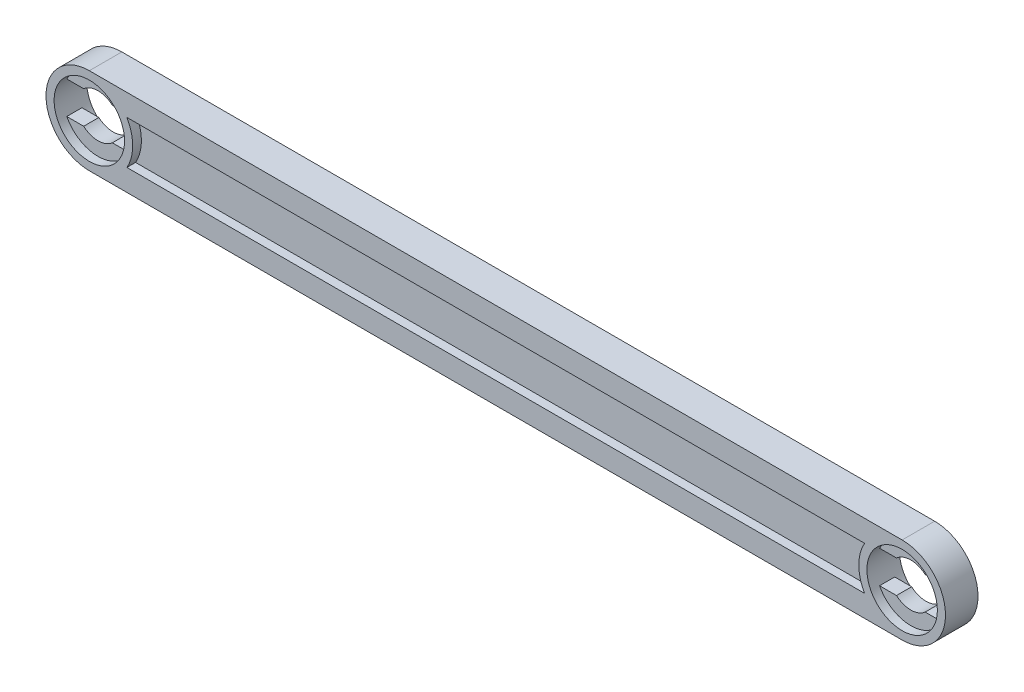
SolidWorks part; units mm, degrees
note: The reader was unsure of these and kept them because the rebuilt part matched: shared geometry of "草图3<2>".
ref_plane "前视基准面" through (0, 0, 0) normal (0, 0, 1) x (1, 0, 0)
ref_plane "上视基准面" through (0, 0, 0) normal (0, 1, 0) x (1, 0, 0)
ref_plane "右视基准面" through (0, 0, 0) normal (1, 0, 0) x (0, 0, -1)
sketch "草图1" plane through (0, 0, 0) normal (0, 0, 1) x (1, 0, 0)
  line L1 (0, 4) -> (75, 4)
  line L3 (0, -4) -> (75, -4)
  arc A0 (0, 4) -> (0, -4) centre (0, 0) ccw
  arc A1 (75, -4) -> (75, 4) centre (75, 0) ccw
extrude "凸台-拉伸1" add sketch "草图1" against normal blind 3
sketch "草图2" plane through (0, 0, 0) normal (0, 0, 1) x (1, 0, 0)
  line L0 (1.3229, -1.5) -> (2.8831, -1.5)
  line L1 (-2.8831, -1.5) -> (-1.3229, -1.5)
  line L2 (1.3229, 1.5) -> (2.8831, 1.5)
  line L3 (-2.8831, 1.5) -> (-1.3229, 1.5)
  arc A0 (1.3229, 1.5) -> (-1.3229, 1.5) centre (0, 0) ccw
  arc A1 (-2.8831, 1.5) -> (-2.8831, -1.5) centre (0, 0) ccw
  arc A3 (2.8831, -1.5) -> (2.8831, 1.5) centre (0, 0) ccw
  arc A4 (-1.3229, -1.5) -> (1.3229, -1.5) centre (0, 0) ccw
extrude "切除-拉伸1" cut sketch "草图2" against normal up to next
sketch "草图3" plane through (0, 0, 0) normal (0, 0, 1) x (1, 0, 0)
  circle A1 centre (0, 0) radius 3.25
extrude "切除-拉伸2" cut sketch "草图3" against normal blind 0.8
extrude "切除-拉伸3" cut sketch "草图3<2>" along normal blind 0.8 from offset 3 offset against normal yes
sketch "草图3<2>" plane through (0, 0, 0) normal (0, 0, 1) x (1, 0, 0) same geometry as "草图3"
ref_plane "基准面1" through (37.5, 0, 0) normal (1, 0, 0) x (0, 0, -1)
mirror "镜向1" about plane through (37.5, 0, 0) normal (1, 0, 0) of "切除-拉伸3", "切除-拉伸2", "切除-拉伸1"
sketch "草图4" plane through (0, 0, 0) normal (0, 0, 1) x (1, 0, 0)
  line L0 (3.4641, 2) -> (71.5359, 2)
  line L2 (3.4641, -2) -> (71.5359, -2)
  arc A0 (3.4641, -2) -> (3.4641, 2) centre (0, 0) ccw
  arc A2 (71.5359, 2) -> (71.5359, -2) centre (75, 0) ccw
extrude "切除-拉伸4" cut sketch "草图4" against normal blind 0.8
sketch "草图5" plane through (0, 0, -3) normal (0, 0, -1) x (-1, 0, 0)
  line L1 (-71, -2) -> (-4, -2)
  line L2 (-71, -2) -> (-71, 2)
  line L3 (-71, 2) -> (-4, 2)
  line L4 (-4, -2) -> (-4, 2)
extrude "切除-拉伸5" cut sketch "草图5" against normal blind 0.8
